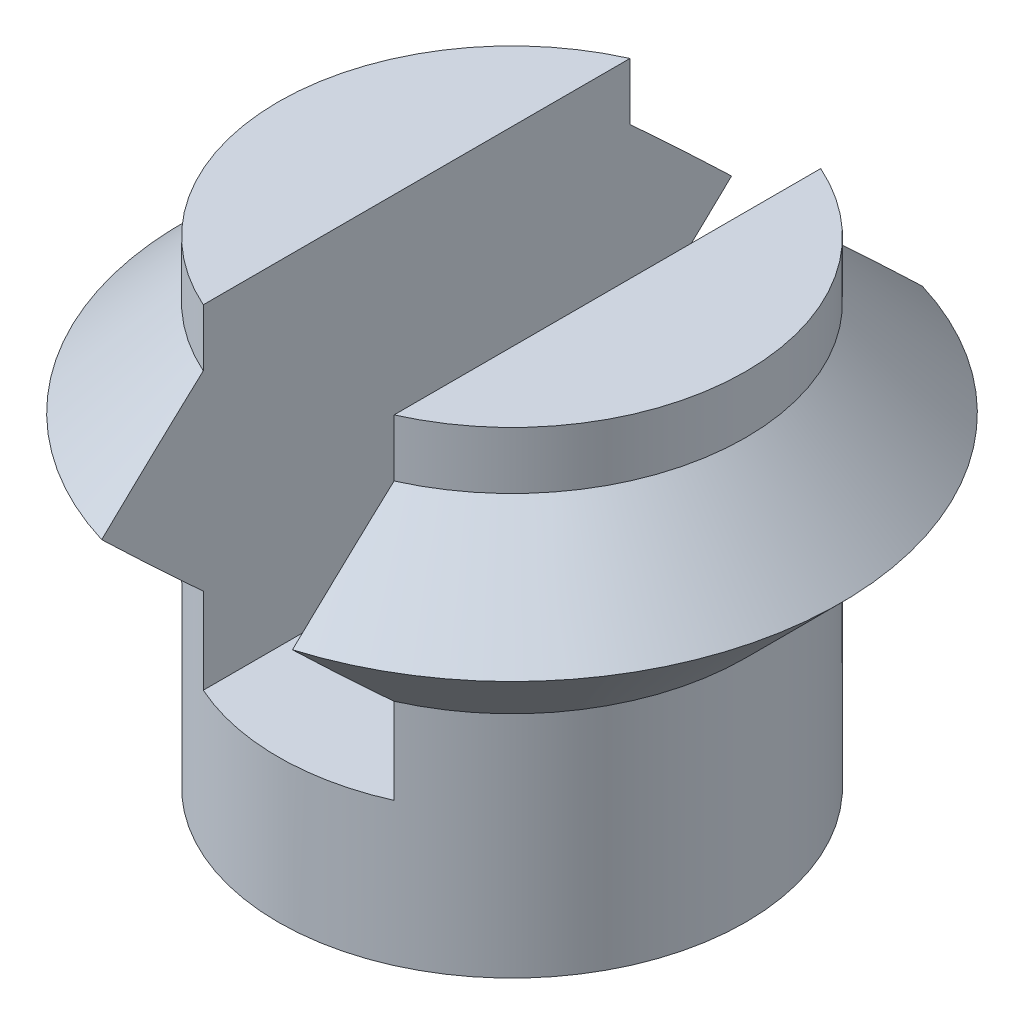
SolidWorks part; units mm, degrees
ref_plane "Спереди" through (0, 0, 0) normal (0, 0, 1) x (1, 0, 0)
ref_plane "Сверху" through (0, 0, 0) normal (0, 1, 0) x (1, 0, 0)
ref_plane "Справа" through (0, 0, 0) normal (1, 0, 0) x (0, 0, -1)
sketch "Sketch1" plane through (0, 0, 0) normal (0, 1, 0) x (1, 0, 0)
  circle A0 centre (0, 0) radius 4.9
  dimension "D1" = 9.8
extrude "Boss-Extrude1" add sketch "Sketch1" along normal blind 3
sketch "Sketch3" plane through (0, 0, 0) normal (0, 0, 1) x (1, 0, 0)
  line L0 (-4.9, 3) -> (-4.9, 4.8)
  line L1 (-4.9, 4.8) -> (-6.9, 6.8)
  line L2 (-6.9, 6.8) -> (-4.9, 8.8)
  line L3 (-4.9, 8.8) -> (-4.9, 10)
  line L4 (-4.9, 10) -> (-1.9, 10)
  line L5 (-1.9, 10) -> (-1.9, 3)
  line L6 (4.9, 3) -> (-4.9, 3) construction
  line L7 (-1.9, 3) -> (-4.9, 3)
  line L8 (-4.9, 0) -> (4.9, 0) construction
  line L9 (0, 0) -> (0, 10.9514) construction
  dimension "D1" = 10
  dimension "D2" = 1.2
  dimension "D3" = 45
  dimension "D4" = 2
  dimension "D5" = 3
revolve "Revolve1" add sketch "Sketch3" angle 360 about L9
sketch "Sketch4" plane through (0, 10, 0) normal (0, 1, 0) x (1, 0, 0)
  line L0 (2, 6.9) -> (-2, 6.9)
  line L1 (-2, 6.9) -> (-2, -6.9)
  line L2 (-2, -6.9) -> (2, -6.9)
  line L3 (0, 6.9) -> (0, -6.9) construction
  line L4 (2, 6.9) -> (2, -6.9)
  circle A0 centre (0, 0) radius 6.9 construction
  dimension "D1" = 2
extrude "Cut-Extrude1" cut sketch "Sketch4" against normal up to surface (7 mm away) up to face at (0, 3, -1.9)
sketch "Sketch6" plane through (0, 0, 0) normal (0, -1, 0) x (1, 0, 0)
  circle A0 centre (0, 0) radius 2.6
  dimension "D1" = 5.2
extrude "Cut-Extrude2" cut sketch "Sketch6" against normal blind 0.6
